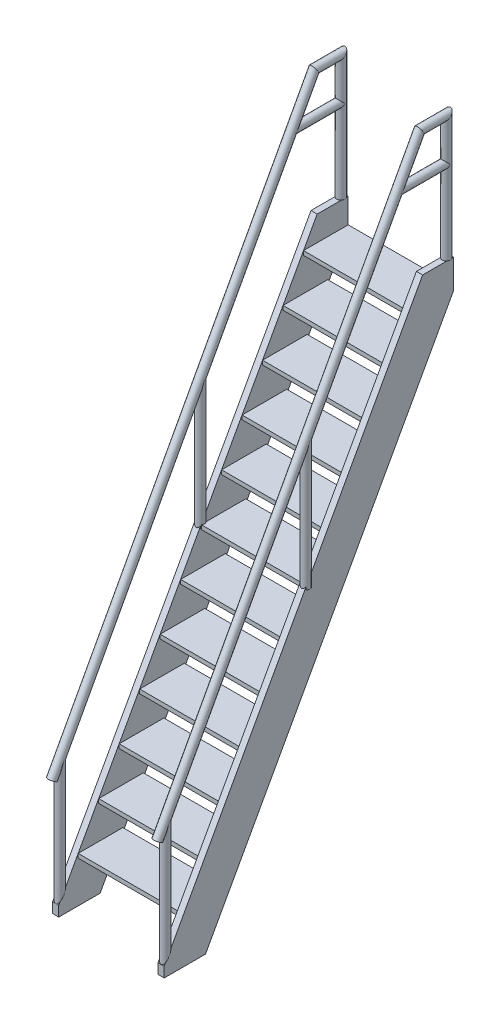
SolidWorks part; units mm, degrees
ref_plane "Front Plane" through (0, 0, 0) normal (0, 0, 1) x (1, 0, 0)
ref_plane "Top Plane" through (0, 0, 0) normal (0, 1, 0) x (1, 0, 0)
ref_plane "Right Plane" through (0, 0, 0) normal (1, 0, 0) x (0, 0, -1)
sketch "Sketch3" plane through (0, 0, 0) normal (1, 0, 0) x (0, 0, -1)
  line L0 (0, 0) -> (-190.5, 0)
  line L1 (0, 0) -> (0, -177.8)
  line L3 (-1778, -2946.4) -> (-1524, -2946.4)
  line L4 (-1778, -2946.4) -> (-1778, -2883.9583)
  line L5 (-1524, -2946.4) -> (0, -177.8)
  line L6 (-190.5, 0) -> (-1778, -2883.9583)
  dimension "D1" = 190.5
  dimension "D2" = 177.8
  dimension "D3" = 1524
  dimension "D4" = 2883.9583
  dimension "D6" = 254
extrude "Boss-Extrude2" add sketch "Sketch3" along normal blind 38.1
sketch "Sketch4" plane through (38.1, 0, 0) normal (1, 0, 0) x (0, 0, -1)
  line L0 (0, -177.8) -> (0, -152.4)
  line L1 (0, -152.4) -> (-274.3899, -152.4)
  line L2 (-190.5, 0) -> (-1778, -2883.9583) construction
  line L3 (-274.3899, -152.4) -> (-274.3899, -177.8)
  line L4 (-274.3899, -177.8) -> (0, -177.8)
  line L5 (-1524, -2946.4) -> (0, -177.8) construction
  line L6 (-125.8349, -406.4) -> (-400.2248, -406.4)
  line L7 (-125.8349, -406.4) -> (-125.8349, -381)
  line L8 (-125.8349, -381) -> (-400.2248, -381)
  line L9 (-400.2248, -406.4) -> (-400.2248, -381)
  line L11 (-251.6697, -635) -> (-526.0596, -635)
  line L12 (-251.6697, -635) -> (-251.6697, -609.6)
  line L13 (-251.6697, -609.6) -> (-526.0596, -609.6)
  line L14 (-526.0596, -635) -> (-526.0596, -609.6)
  line L15 (-377.5046, -863.6) -> (-651.8945, -863.6)
  line L16 (-377.5046, -863.6) -> (-377.5046, -838.2)
  line L17 (-377.5046, -838.2) -> (-651.8945, -838.2)
  line L18 (-651.8945, -863.6) -> (-651.8945, -838.2)
  line L19 (-503.3394, -1092.2) -> (-777.7294, -1092.2)
  line L20 (-503.3394, -1092.2) -> (-503.3394, -1066.8)
  line L21 (-503.3394, -1066.8) -> (-777.7294, -1066.8)
  line L22 (-777.7294, -1092.2) -> (-777.7294, -1066.8)
  line L23 (-629.1743, -1320.8) -> (-903.5642, -1320.8)
  line L24 (-629.1743, -1320.8) -> (-629.1743, -1295.4)
  line L25 (-629.1743, -1295.4) -> (-903.5642, -1295.4)
  line L26 (-903.5642, -1320.8) -> (-903.5642, -1295.4)
  line L27 (-755.0092, -1549.4) -> (-1029.3991, -1549.4)
  line L28 (-755.0092, -1549.4) -> (-755.0092, -1524)
  line L29 (-755.0092, -1524) -> (-1029.3991, -1524)
  line L30 (-1029.3991, -1549.4) -> (-1029.3991, -1524)
  line L31 (-880.844, -1778) -> (-1155.2339, -1778)
  line L32 (-880.844, -1778) -> (-880.844, -1752.6)
  line L33 (-880.844, -1752.6) -> (-1155.2339, -1752.6)
  line L34 (-1155.2339, -1778) -> (-1155.2339, -1752.6)
  line L35 (-1006.6789, -2006.6) -> (-1281.0688, -2006.6)
  line L36 (-1006.6789, -2006.6) -> (-1006.6789, -1981.2)
  line L37 (-1006.6789, -1981.2) -> (-1281.0688, -1981.2)
  line L38 (-1281.0688, -2006.6) -> (-1281.0688, -1981.2)
  line L39 (-1132.5138, -2235.2) -> (-1406.9037, -2235.2)
  line L40 (-1132.5138, -2235.2) -> (-1132.5138, -2209.8)
  line L41 (-1132.5138, -2209.8) -> (-1406.9037, -2209.8)
  line L42 (-1406.9037, -2235.2) -> (-1406.9037, -2209.8)
  line L43 (-1258.3486, -2463.8) -> (-1532.7385, -2463.8)
  line L44 (-1258.3486, -2463.8) -> (-1258.3486, -2438.4)
  line L45 (-1258.3486, -2438.4) -> (-1532.7385, -2438.4)
  line L46 (-1532.7385, -2463.8) -> (-1532.7385, -2438.4)
  line L47 (-1384.1835, -2692.4) -> (-1658.5734, -2692.4)
  line L48 (-1384.1835, -2692.4) -> (-1384.1835, -2667)
  line L49 (-1384.1835, -2667) -> (-1658.5734, -2667)
  line L50 (-1658.5734, -2692.4) -> (-1658.5734, -2667)
  dimension "D1" = 25.4
  dimension "D2" = 228.6
  dimension "D3" = 228.6
  dimension "D4" = 228.6
  dimension "D5" = 228.6
  dimension "D6" = 228.6
  dimension "D7" = 228.6
  dimension "D8" = 228.6
  dimension "D9" = 228.6
  dimension "D10" = 228.6
  dimension "D11" = 228.6
  dimension "D12" = 228.6
extrude "Boss-Extrude3" add sketch "Sketch4" along normal blind 304.8
sketch "Sketch5" plane through (0, -2667, 0) normal (0, 1, 0) x (1, 0, 0)
  line L0 (38.1, -1778) -> (0, -1778) construction
  circle A0 centre (19.05, -1752.6) radius 25.4
  dimension "D1" = 50.8
  dimension "D2" = 25.4
extrude "Boss-Extrude4" add sketch "Sketch5" against normal up to surface and the other way blind 544.5785 up to face at (33.3375, -1417.7698, 970.9237)
sketch "Sketch6" plane through (0, 0, 0) normal (0, 1, 0) x (1, 0, 0)
  line L0 (38.1, 0) -> (0, 0) construction
  circle A0 centre (19.05, -25.4) radius 25.4
  dimension "D1" = 50.8
  dimension "D2" = 25.4
extrude "Boss-Extrude5" add sketch "Sketch6" along normal blind 762
ref_plane "Plane3" through (0, 0, 25.4) normal (0, 0, -1) x (-1, 0, 0)
sketch "Sketch7" plane through (0, 0, 25.4) normal (0, 0, -1) x (-1, 0, 0)
  line L0 (6.35, 762) -> (-44.45, 762) construction
  circle A0 centre (-19.05, 762) radius 25.4
extrude "Boss-Extrude6" add sketch "Sketch7" along normal up to surface (25.4 mm away) up to face at (19.05, 762, 50.8)
extrude "Boss-Extrude7" add sketch "Sketch7<2>" against normal blind 165.1
sketch "Sketch7<2>" plane through (0, 0, 25.4) normal (0, 0, -1) x (-1, 0, 0) same geometry as "Sketch7"
ref_plane "Plane4" through (19.05, 0, 0) normal (-1, 0, 0) x (0, 0, 1)
sketch "Sketch8" plane through (19.05, 0, 0) normal (-1, 0, 0) x (0, 0, 1)
  line L0 (190.5, 762) -> (1752.6, -2122.4215)
  line L1 (190.5, 736.6) -> (190.5, 787.4) construction
  line L2 (1778, -2122.4215) -> (1727.2, -2122.4215) construction
ref_plane "Plane5" through (19.05, 762, 190.5) normal (0, -0.8793, 0.4762) x (1, 0, 0)
sketch "Sketch9" plane through (19.05, 762, 190.5) normal (0, -0.8793, 0.4762) x (1, 0, 0)
  circle A0 centre (0, 0) radius 25.4
  dimension "D1" = 50.8
extrude "Boss-Extrude8" add sketch "Sketch9" along normal blind 3382.01 and the other way up to surface other way up to face at (19.05, 736.6, 50.8)
sketch "Sketch12" plane through (0, 0, 0) normal (-1, 0, 0) x (0, 0, 1)
  line L0 (0, -88.9) -> (0, -1160.8117)
  line L1 (0, -177.8) -> (0, 0) construction
  line L2 (0, -1160.8117) -> (889, -1160.8117)
  dimension "D1" = 889
sketch "Sketch14" plane through (0, -1066.8, 0) normal (0, 1, 0) x (1, 0, 0)
  line L2 (19.05, -190.5) -> (19.05, -1752.6) construction
  circle A0 centre (19.05, -889) radius 25.4
extrude "Boss-Extrude14" add sketch "Sketch14" along normal up to next and the other way blind 251.714
sketch "Sketch15" plane through (0, 0, 25.4) normal (0, 0, -1) x (-1, 0, 0)
  line L0 (-19.05, 762) -> (-19.05, -2122.4215) construction
  circle A0 centre (-19.05, 508) radius 25.4
  dimension "D1" = 254
extrude "Boss-Extrude15" add sketch "Sketch15" against normal up to surface (260.016 mm away) up to face at (19.05, -581.1194, 889)
ref_plane "Plane2" through (342.9, 0, 0) normal (1, 0, 0) x (0, 0, -1)
mirror "Mirror5" about plane through (342.9, 0, 0) normal (1, 0, 0) of bodies 114 103
